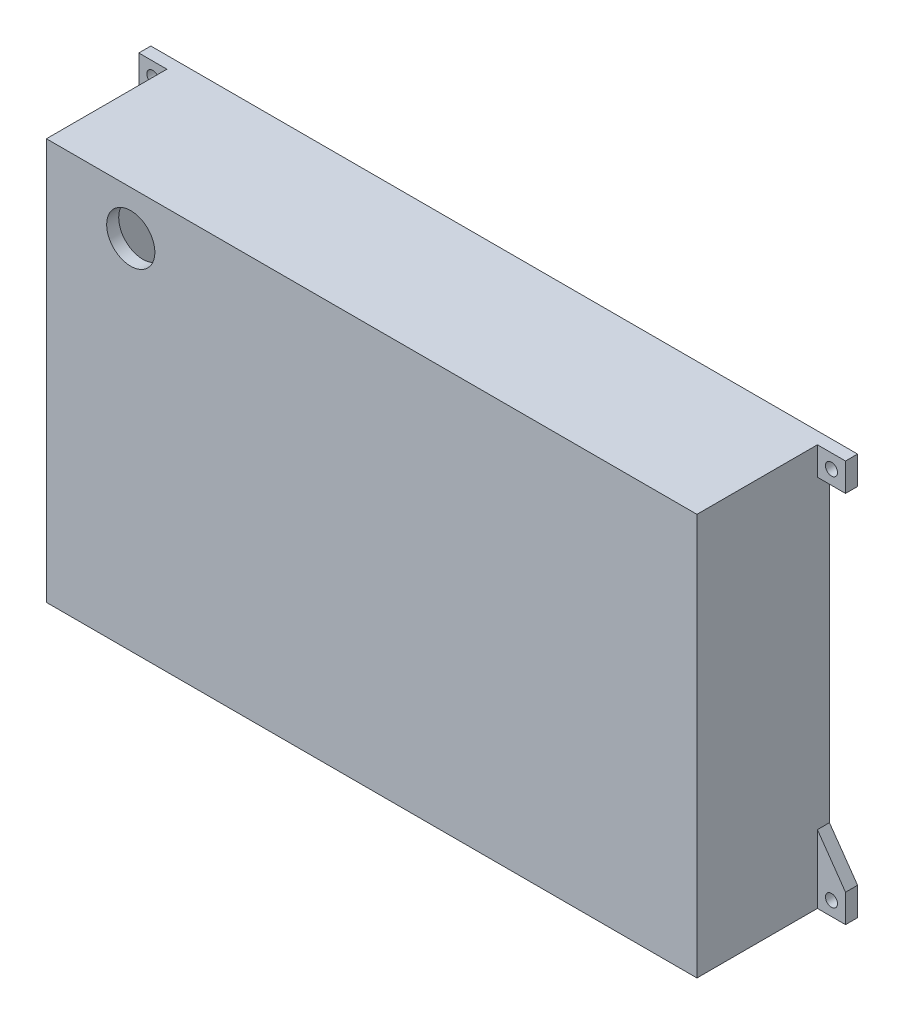
SolidWorks part; units mm, degrees
ref_plane "Front Plane" through (0, 0, 0) normal (0, 0, 1) x (1, 0, 0)
ref_plane "Top Plane" through (0, 0, 0) normal (0, 1, 0) x (1, 0, 0)
ref_plane "Right Plane" through (0, 0, 0) normal (1, 0, 0) x (0, 0, -1)
sketch "Sketch1" plane through (0, 0, 0) normal (0, 0, 1) x (1, 0, 0)
  line L0 (165.5, 100) -> (165.5, 93)
  line L1 (0, 0) -> (162, 0)
  line L3 (0, 100) -> (162, 100)
  line L4 (162, 0) -> (162, 100)
  line L5 (162, 100) -> (169, 100)
  line L6 (162, 100) -> (162, 93)
  line L7 (162, 93) -> (169, 93)
  line L8 (169, 100) -> (169, 93)
  line L9 (81, 100) -> (81, 0) construction
  line L10 (0, 50) -> (162, 50) construction
  line L11 (169, 0) -> (169, 7)
  line L13 (162, 0) -> (162, 7)
  line L14 (162, 0) -> (169, 0)
  line L15 (0, 0) -> (-7, 0)
  line L16 (0, 0) -> (0, 7)
  line L18 (-7, 0) -> (-7, 7)
  line L19 (-7, 100) -> (-7, 93)
  line L20 (0, 93) -> (-7, 93)
  line L22 (0, 100) -> (-7, 100)
  line L23 (-7, 7) -> (0, 17)
  line L24 (-3.5, 100) -> (-3.5, 93)
  line L25 (0, 0) -> (0, 7)
  line L26 (0, 7) -> (0, 17)
  line L27 (0, 17) -> (0, 93)
  line L28 (0, 93) -> (0, 100)
  line L29 (162, 7) -> (162, 17)
  line L30 (169, 7) -> (162, 17)
  circle A0 centre (165.5, 96.5) radius 1.5
  circle A1 centre (165.5, 3.5) radius 1.5
  circle A2 centre (-3.5, 3.5) radius 1.5
  circle A3 centre (-3.5, 96.5) radius 1.5
  dimension "D5" = 10
  dimension "D1" = 162
  dimension "D2" = 100
  dimension "D3" = 7
  dimension "D4" = 7
extrude "Boss-Extrude1" add sketch "Sketch1" along normal blind 33 contours L1 L4 L3 region at (81, 50, 0)
extrude "Boss-Extrude2" add sketch "Sketch1<4>" along normal blind 3 contours L24 A3 L20 L22 | L24 A3 L22 L19 L20 | L18 L15 A2 | L4 L14 L11 A1 | A0 L0 L7 L8 L5 | A0 L0 L5 L4 L7 region at (167.4377, 96.5, 0) region at (163.5623, 96.5, 0) region at (-1.5623, 96.5, 0) region at (-5.4377, 96.5, 0) region at (164.9692, 6.6088, 0) region at (-2.9692, 6.6088, 0)
sketch "Sketch1<4>" plane through (0, 0, 0) normal (0, 0, 1) x (1, 0, 0) same geometry as "Sketch1"
sketch "Sketch3" plane through (0, 0, 0) normal (0, 0, -1) x (-1, 0, 0)
  line L0 (0, 100) -> (-162, 100) construction
  line L5 (0, 0) -> (0, 100) construction
  line L6 (-159, 97) -> (-3, 97)
  line L7 (-159, 97) -> (-159, 0)
  line L8 (-159, 0) -> (-3, 0)
  line L9 (-3, 97) -> (-3, 0)
  line L10 (-162, 0) -> (-162, 100) construction
  line L11 (-81, 97) -> (-81, 0) construction
  circle A0 centre (-21, 89) radius 6
  point P6 (-31, 77)
  dimension "D5" = 8
  dimension "D1" = 3
  dimension "D2" = 3
  dimension "D3" = 3
  dimension "D4" = 97
extrude "Cut-Extrude1" cut sketch "Sketch3" against normal blind 30 contours L7 L8 L9 L6
extrude "Cut-Extrude2" cut sketch "Sketch3<4>" against normal blind 33 contours A0
sketch "Sketch3<4>" plane through (0, 0, 0) normal (0, 0, -1) x (-1, 0, 0) same geometry as "Sketch3"
sketch "Sketch4" plane through (162, 0, 0) normal (1, 0, 0) x (0, 0, -1)
  line L0 (-30, 97) -> (-30, 0) construction
  circle A0 centre (-24.5, 91.491) radius 5.5
  dimension "D1" = 11
  dimension "D2" = 5.5
sketch "Sketch6" plane through (0, 0, 30) normal (0, 0, -1) x (-1, 0, 0)
  line L0 (-159, 97) -> (-3, 97) construction
  line L3 (-130.5, 85) -> (-125.5, 85)
  line L5 (-125.5, 85) -> (-115.5, 97)
  line L10 (-130.5, 97) -> (-130.5, 85)
  line L11 (-115.5, 97) -> (-130.5, 97)
  line L13 (-162, 17) -> (-162, 93) construction
  dimension "D1" = 31.5
  dimension "D2" = 5
  dimension "D3" = 15
